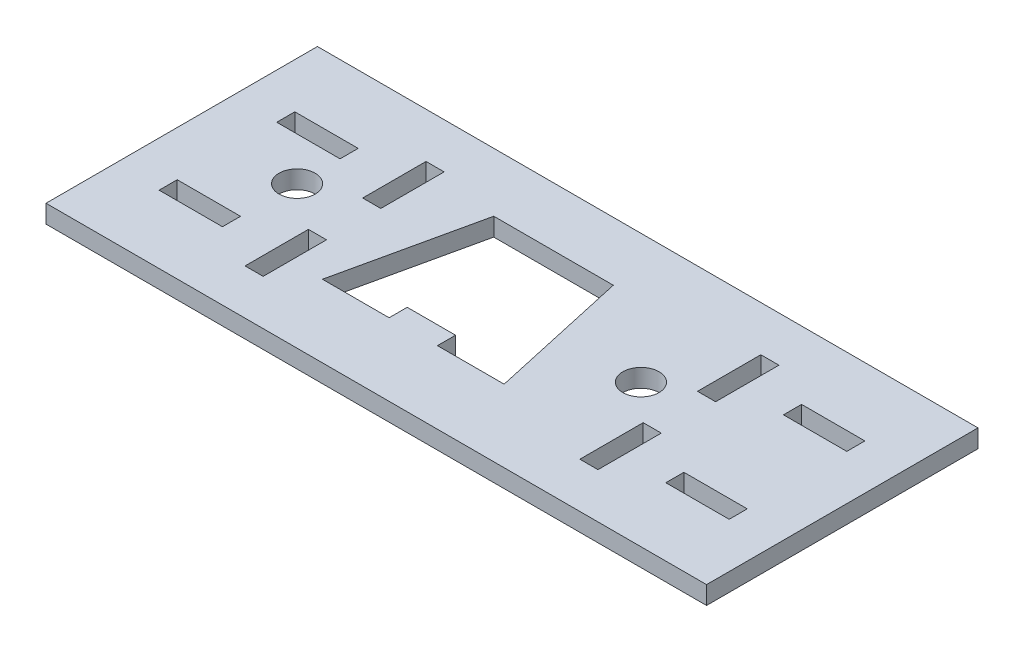
SolidWorks part; units mm, degrees
ref_plane "Front Plane" through (0, 0, 0) normal (0, 0, 1) x (1, 0, 0)
ref_plane "Top Plane" through (0, 0, 0) normal (0, 1, 0) x (1, 0, 0)
ref_plane "Right Plane" through (0, 0, 0) normal (1, 0, 0) x (0, 0, -1)
sketch "Sketch1" plane through (0, 0, 0) normal (0, 1, 0) x (1, 0, 0)
  line L1 (-47.7698, 5.0859) -> (25.2302, 5.0859)
  line L2 (-47.7698, 5.0859) -> (-47.7698, -24.9141)
  line L3 (-47.7698, -24.9141) -> (25.2302, -24.9141)
  line L4 (25.2302, 5.0859) -> (25.2302, -24.9141)
  line L5 (-42.7698, -15.4141) -> (-35.7698, -15.4141)
  line L6 (-42.7698, -15.4141) -> (-42.7698, -17.4141)
  line L7 (-42.7698, -17.4141) -> (-35.7698, -17.4141)
  line L8 (-35.7698, -15.4141) -> (-35.7698, -17.4141)
  line L9 (-42.7698, -2.4141) -> (-35.7698, -2.4141)
  line L10 (-42.7698, -2.4141) -> (-42.7698, -4.4141)
  line L11 (-42.7698, -4.4141) -> (-35.7698, -4.4141)
  line L12 (-35.7698, -2.4141) -> (-35.7698, -4.4141)
  line L13 (13.2302, -2.4141) -> (20.2302, -2.4141)
  line L14 (13.2302, -2.4141) -> (13.2302, -4.4141)
  line L15 (13.2302, -4.4141) -> (20.2302, -4.4141)
  line L16 (20.2302, -2.4141) -> (20.2302, -4.4141)
  line L17 (13.2302, -15.4141) -> (20.2302, -15.4141)
  line L18 (13.2302, -15.4141) -> (13.2302, -17.4141)
  line L19 (13.2302, -17.4141) -> (20.2302, -17.4141)
  line L20 (20.2302, -15.4141) -> (20.2302, -17.4141)
  line L21 (-30.7698, 0.0859) -> (-28.7698, 0.0859)
  line L22 (-30.7698, 0.0859) -> (-30.7698, -6.9141)
  line L23 (-30.7698, -6.9141) -> (-28.7698, -6.9141)
  line L24 (-28.7698, 0.0859) -> (-28.7698, -6.9141)
  line L25 (-30.7698, -12.9141) -> (-28.7698, -12.9141)
  line L26 (-30.7698, -12.9141) -> (-30.7698, -19.9141)
  line L27 (-30.7698, -19.9141) -> (-28.7698, -19.9141)
  line L28 (-28.7698, -12.9141) -> (-28.7698, -19.9141)
  line L29 (8.2302, -19.9141) -> (6.2302, -19.9141)
  line L30 (8.2302, -19.9141) -> (8.2302, -12.9141)
  line L31 (8.2302, -12.9141) -> (6.2302, -12.9141)
  line L32 (6.2302, -19.9141) -> (6.2302, -12.9141)
  line L33 (8.2302, -6.9141) -> (6.2302, -6.9141)
  line L34 (8.2302, -6.9141) -> (8.2302, 0.0859)
  line L35 (8.2302, 0.0859) -> (6.2302, 0.0859)
  line L36 (6.2302, -6.9141) -> (6.2302, 0.0859)
  dimension "D21" = 7
  dimension "D22" = 7
  dimension "D24" = 7
  dimension "D25" = 2
  dimension "D27" = 2
  dimension "D29" = 5
  dimension "D31" = 5
  dimension "D1" = 30
  dimension "D2" = 73
  dimension "D3" = 7
  dimension "D4" = 7
  dimension "D5" = 7
  dimension "D6" = 7
  dimension "D7" = 2
  dimension "D8" = 2
  dimension "D9" = 2
  dimension "D10" = 2
  dimension "D11" = 5
  dimension "D12" = 5
  dimension "D13" = 5
  dimension "D14" = 5
  dimension "D15" = 7.5
  dimension "D16" = 7.5
  dimension "D17" = 11
  dimension "D18" = 7.5
  dimension "D19" = 11
  dimension "D20" = 7.5
  dimension "D23" = 7
  dimension "D26" = 2
  dimension "D28" = 2
  dimension "D30" = 5
  dimension "D32" = 5
  dimension "D33" = 5
  dimension "D34" = 5
  dimension "D35" = 6
  dimension "D36" = 5
  dimension "D37" = 5
  dimension "D38" = 6
extrude "Boss-Extrude1" add sketch "Sketch1" along normal blind 2
sketch "Sketch3" plane through (0, 2, 0) normal (0, 1, 0) x (1, 0, 0)
  line L0 (-12.5088, -14.9141) -> (-12.5088, -16.9141)
  line L1 (-17.8505, -14.9141) -> (-12.5088, -14.9141)
  line L2 (-12.5088, -14.9141) -> (-7.6302, -14.9141)
  line L3 (-7.6302, -14.9141) -> (-10.1796, -3.4141)
  line L4 (-10.1796, -3.4141) -> (-20.1796, -3.4141)
  line L5 (-20.1796, -3.4141) -> (-22.7291, -14.9141)
  line L6 (-22.7291, -14.9141) -> (-17.8505, -14.9141)
  line L7 (-17.8505, -14.9141) -> (-17.8505, -16.9141)
  line L9 (-17.8505, -16.9141) -> (-25.2211, -16.9141)
  line L10 (-25.2211, -16.9141) -> (-21.7848, -1.4141)
  line L11 (-21.7848, -1.4141) -> (-8.5745, -1.4141)
  line L12 (-8.5745, -1.4141) -> (-5.1382, -16.9141)
  line L13 (-5.1382, -16.9141) -> (-12.5088, -16.9141)
  dimension "D1" = 2
  dimension "D2" = 2
  dimension "D3" = 2
  dimension "D4" = 2
  dimension "D5" = 2
  dimension "D6" = 13.2103
  dimension "D7" = 15.8763
  dimension "D8" = 11.7792
  dimension "D9" = 4.8786
  dimension "D10" = 7.3706
  dimension "D11" = 2
  dimension "D12" = 4.8786
  dimension "D13" = 11.7792
  dimension "D14" = 15.8763
  dimension "D15" = 7.3706
  dimension "D16" = 10
  dimension "D17" = 13.2103
  dimension "D18" = 0
extrude "Cut-Extrude1" cut sketch "Sketch3" against normal blind 10 contours L5 L6 L1 L2 L3 L4 | L13 L12 L11 L10 L9 L7 L6 L5 L4 L3 L2 L0 region at (-10.0695, 2, 15.1678) region at (-15.1796, 2, 9.5535)
sketch "Sketch6" plane through (0, 2, 0) normal (0, 1, 0) x (1, 0, 0)
  line L0 (-30.7698, -12.9141) -> (-30.7698, -19.9141) construction
  line L1 (-35.7698, -15.4141) -> (-42.7698, -15.4141) construction
  line L3 (6.2302, -12.9141) -> (6.2302, -19.9141) construction
  circle A0 centre (-35.7698, -9.1641) radius 2
  circle A1 centre (2.2302, -9.1641) radius 2
  point P4 (0.8289, -9.337)
  dimension "D1" = 4
  dimension "D2" = 4
  dimension "D3" = 5
  dimension "D4" = 6.25
  dimension "D5" = 6.25
  dimension "D6" = 4
extrude "Cut-Extrude2" cut sketch "Sketch6" against normal blind 19
